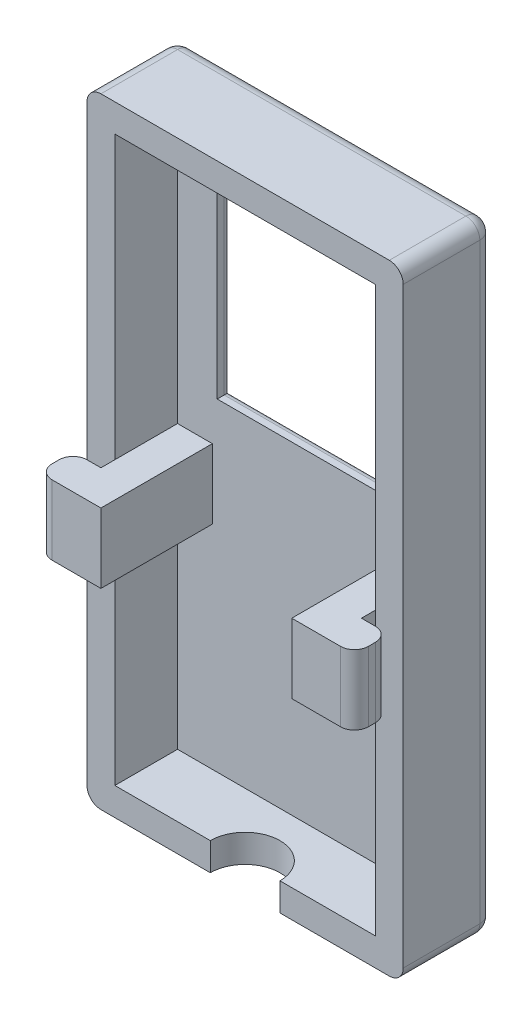
SolidWorks part; units mm, degrees
ref_plane "Front Plane" through (0, 0, 0) normal (0, 0, 1) x (1, 0, 0)
ref_plane "Top Plane" through (0, 0, 0) normal (0, 1, 0) x (1, 0, 0)
ref_plane "Right Plane" through (0, 0, 0) normal (1, 0, 0) x (0, 0, -1)
sketch "Sketch1" plane through (0, 0, 0) normal (0, 0, 1) x (1, 0, 0)
  line L1 (-11.35, 22.25) -> (11.35, 22.25)
  line L2 (-11.35, 22.25) -> (-11.35, -22.25)
  line L3 (-11.35, -22.25) -> (11.35, -22.25)
  line L4 (11.35, 22.25) -> (11.35, -22.25)
  line L5 (-11.35, 22.25) -> (11.35, -22.25) construction
  line L6 (-11.35, -22.25) -> (11.35, 22.25) construction
  point P0 (0, 0)
  dimension "D1" = 22.7
  dimension "D2" = 44.5
extrude "Boss-Extrude1" add sketch "Sketch1" along normal blind 2
sketch "Sketch2" plane through (0, 0, 2) normal (0, 0, 1) x (1, 0, 0)
  line L1 (-11.35, 22.25) -> (11.35, 22.25)
  line L2 (-11.35, 22.25) -> (-11.35, -22.25)
  line L3 (-11.35, -22.25) -> (11.35, -22.25)
  line L4 (11.35, 22.25) -> (11.35, -22.25)
  line L5 (-9.35, 20.25) -> (9.35, 20.25)
  line L6 (-9.35, 20.25) -> (-9.35, -20.25)
  line L7 (-9.35, -20.25) -> (9.35, -20.25)
  line L8 (9.35, 20.25) -> (9.35, -20.25)
  dimension "D1" = 2
  dimension "D2" = 2
  dimension "D3" = 2
  dimension "D4" = 2
extrude "Boss-Extrude2" add sketch "Sketch2" along normal blind 4.5
sketch "Sketch3" plane through (-9.35, 0, 0) normal (1, 0, 0) x (0, 0, -1)
  line L1 (-2, 0) -> (-2, -5)
  line L2 (-2, -5) -> (-10, -5)
  line L13 (-10, -5) -> (-10, 0)
  line L17 (-10, 0) -> (-10, -2.5)
  line L20 (-2, 20.25) -> (-2, -20.25) construction
  line L21 (-2, 0) -> (-2, -2.5)
  line L23 (-10, 0) -> (-2, 0)
  line M5 (-2, -20.25) -> (-2, 20.25)
  line M7 (-6.5, 20.25) -> (-6.5, -20.25)
  dimension "D2" = 5
extrude "Boss-Extrude3" add sketch "Sketch3" along normal blind 2.5 contours L23 L13 L2 M7 | L23 L2 L1 M7 M5 region at (-9.35, -2.5, 4.25) region at (-9.35, -2.5, 8.25)
sketch "Sketch4" plane through (9.35, 0, 0) normal (-1, 0, 0) x (0, 0, 1)
  line L0 (2, 0) -> (2, -5)
  line L2 (2, -20.25) -> (2, 20.25) construction
  line L3 (2, 0) -> (2, -2.5)
  line L4 (2, -2.5) -> (2, 0)
  line L6 (10, -2.5) -> (10, 0)
  line L8 (2, -5) -> (10, -5)
  line L9 (10, -5) -> (10, 0)
  line L10 (10, 0) -> (2, 0)
  line M4 (2, 20.25) -> (2, -20.25)
  line M6 (6.5, -20.25) -> (6.5, 20.25)
  dimension "D1" = 2.5
  dimension "D3" = 8
  dimension "D4" = 5
extrude "Boss-Extrude4" add sketch "Sketch4" along normal blind 2.5 contours L6 M6 | M6 M4 region at (9.35, -2.5, 4.25) region at (9.35, -2.5, 8.25)
sketch "Sketch5" plane through (9.35, 0, 0) normal (1, 0, 0) x (0, 0, -1)
  line L5 (-6.5, -5) -> (-10, -5) construction
  line L6 (-10, 0) -> (-7.5, 0)
  line L7 (-10, 0) -> (-10, -5)
  line L8 (-10, -5) -> (-7.5, -5)
  line L9 (-7.5, 0) -> (-7.5, -5)
  dimension "D1" = 2.5
extrude "Boss-Extrude5" add sketch "Sketch5" along normal blind 2
sketch "Sketch7" plane through (0, 0, 2) normal (0, 0, 1) x (1, 0, 0)
  line L1 (-6.5, 3.95) -> (-6.5, 2.95)
  line L3 (-6.5, 2.95) -> (6.5, 2.95)
  line L7 (6.5, 2.95) -> (6.5, 3.95)
  line L10 (-6.5, 16.95) -> (-6.5, 3.95)
  line L12 (6.5, 16.95) -> (6.5, 3.95)
  line L14 (6.5, 16.95) -> (-6.5, 16.95)
  point P0 (0, 8.95)
  dimension "D3" = 1
extrude "Cut-Extrude1" cut sketch "Sketch7" against normal through all
sketch "Sketch8" plane through (-9.35, 0, 0) normal (-1, 0, 0) x (0, 0, 1)
  line L0 (6.5, -5) -> (10, -5) construction
  line L1 (10, 0) -> (7.5, 0)
  line L2 (10, 0) -> (10, -5)
  line L3 (10, -5) -> (7.5, -5)
  line L4 (7.5, 0) -> (7.5, -5)
  dimension "D1" = 2.5
extrude "Boss-Extrude7" add sketch "Sketch8" along normal blind 2
fillet "Fillet2" radius 1 4 edges at (11.35, -2.5, 10) (11.35, -2.5, 7.5) (-11.35, -2.5, 7.5) (-11.35, -2.5, 10)
fillet "Fillet3" radius 1 8 edges at (11.35, -22.25, 3.25) (0, -22.25, 0) (-11.35, -22.25, 3.25) (-11.35, 0, 0) (-11.35, 22.25, 3.25) (11.35, 0, 0) (0, 22.25, 0) (11.35, 22.25, 3.25)
sketch "Sketch9" plane through (0, 0, 0) normal (0, 0, -1) x (-1, 0, 0)
  line L15 (-6.5, 16.95) -> (6.5, 16.95)
  line L17 (-6.5, 16.95) -> (-6.5, 2.95)
  line L18 (-6.5, 2.95) -> (6.5, 2.95)
  line L19 (6.5, 16.95) -> (6.5, 2.95)
  line L21 (-7.5, 17.95) -> (7.5, 17.95)
  line L22 (-7.5, 17.95) -> (-7.5, 1.95)
  line L23 (-7.5, 1.95) -> (7.5, 1.95)
  line L24 (7.5, 17.95) -> (7.5, 1.95)
  point P0 (0, 8.95)
  point P13 (0, 8.95)
  dimension "D1" = 1
  dimension "D2" = 1
  dimension "D3" = 1
  dimension "D4" = 1
sketch "Sketch12" plane through (0, 0, 2) normal (0, 0, 1) x (1, 0, 0)
  line L0 (5.05, -5.65) -> (5.05, -20.25)
  line L2 (-9.35, -20.25) -> (9.35, -20.25) construction
  line L3 (9.35, -20.25) -> (9.35, -5) construction
  circle A1 centre (5.05, -5.65) radius 1.6
  dimension "D5" = 3.2
  dimension "D1" = 14.6
  dimension "D2" = 4.3
extrude "Cut-Extrude7" cut sketch "Sketch12" against normal through all contours A1 region at (6.1494, -6.7494, 2)
extrude "Cut-Extrude9" cut sketch "Sketch9" against normal blind 1
fillet "Fillet8" radius 0.5 9 edges at (6.65, -5.65, 0) (0, 16.95, 1) (0, 17.95, 0) (7.5, 9.95, 0) (6.5, 9.95, 1) (-6.5, 9.95, 1) (0, 2.95, 1) (0, 1.95, 0) (-7.5, 9.95, 0)
sketch "Sketch14" plane through (0, -20.25, 0) normal (0, 1, 0) x (1, 0, 0)
  line L0 (10.35, -6.5) -> (-10.35, -6.5) construction
  line L1 (-2.5, -6.5) -> (2.5, -6.5)
  arc A0 (2.5, -6.5) -> (-2.5, -6.5) centre (0, -6.5) ccw
  dimension "D1" = 5
extrude "Cut-Extrude10" cut sketch "Sketch14" against normal through all
sketch "Sketch17" plane through (0, 0, 0) normal (0, 0, -1) x (-1, 0, 0)
  text T0 "Meritus" font "Book Antiqua" height in points 8
extrude "Cut-Extrude11" cut sketch "Sketch17" against normal blind 1
sketch "Sketch18" plane through (0, 0, 0) normal (0, 0, -1) x (-1, 0, 0)
  text T0 "Humidity detector" font "Centaur" height in points 8
extrude "Cut-Extrude12" cut sketch "Sketch18" against normal blind 1
